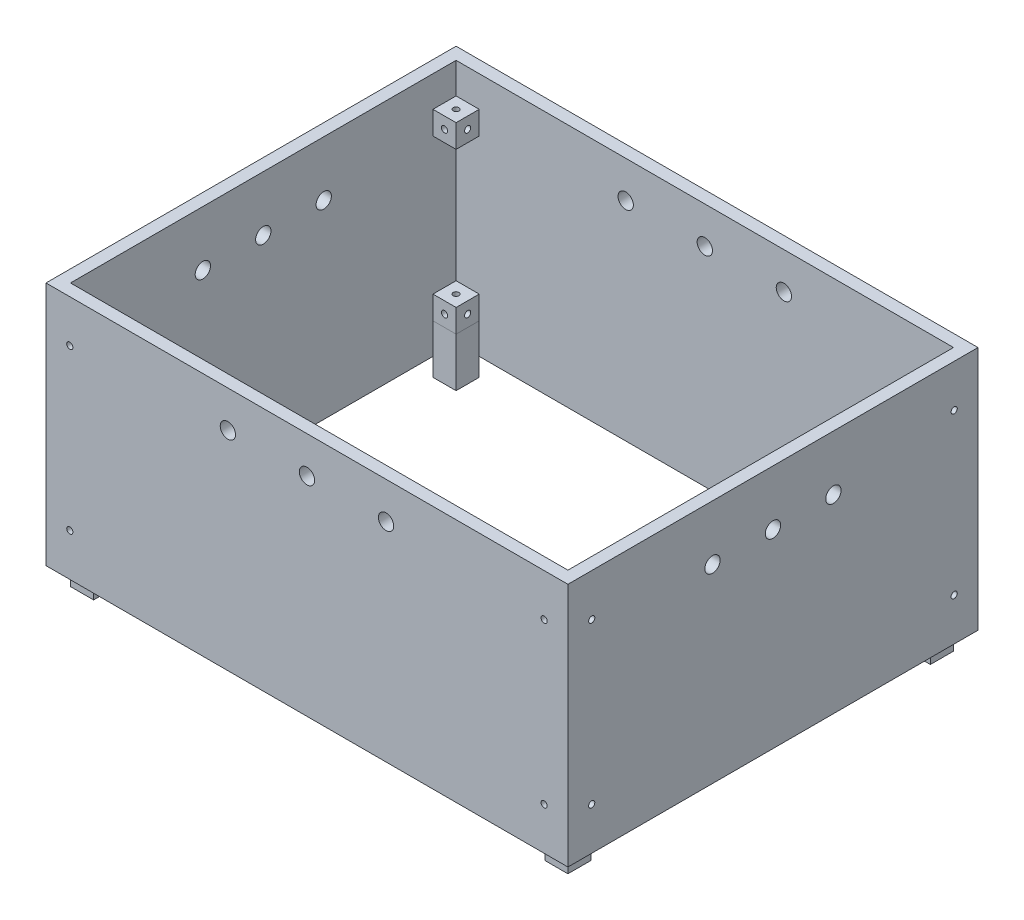
SolidWorks part; units mm, degrees
ref_plane "Front Plane" through (0, 0, 0) normal (0, 0, 1) x (1, 0, 0)
ref_plane "Top Plane" through (0, 0, 0) normal (0, 1, 0) x (1, 0, 0)
ref_plane "Right Plane" through (0, 0, 0) normal (1, 0, 0) x (0, 0, -1)
sketch "Sketch1" plane through (0, 0, 0) normal (0, 1, 0) x (1, 0, 0)
  line L1 (0, 0) -> (270.7, 0)
  line L2 (0, 0) -> (0, 212.7)
  line L3 (0, 212.7) -> (270.7, 212.7)
  line L4 (270.7, 0) -> (270.7, 212.7)
  line L5 (6.35, 6.35) -> (264.35, 6.35)
  line L6 (6.35, 6.35) -> (6.35, 206.35)
  line L7 (6.35, 206.35) -> (264.35, 206.35)
  line L8 (264.35, 6.35) -> (264.35, 206.35)
  dimension "D3" = 6.35
  dimension "D4" = 6.35
  dimension "D5" = 6.35
  dimension "D6" = 6.35
  dimension "D1" = 258
  dimension "D2" = 200
extrude "Walls" add sketch "Sketch1" along normal blind 127
sketch "Sketch2" plane through (0, 0, 0) normal (0, 0, 1) x (1, 0, 0)
  line L0 (0, 127) -> (270.7, 127) construction
  line L1 (135.35, 127) -> (135.35, 107.95) construction
  line L2 (94.33, 127) -> (94.33, 107.95) construction
  line L3 (0, 127) -> (0, 0) construction
  line L4 (176.3667, 127) -> (176.3667, 107.95) construction
  line L5 (270.7, 127) -> (270.7, 0) construction
  circle A0 centre (135.35, 107.95) radius 3.9687
  circle A1 centre (94.33, 107.95) radius 3.9687
  circle A2 centre (176.3667, 107.95) radius 3.9687
  dimension "D2" = 7.9375
  dimension "D4" = 7.9375
  dimension "D7" = 7.9375
  dimension "D1" = 19.05
  dimension "D3" = 94.33
  dimension "D5" = 19.05
  dimension "D6" = 94.3333
  dimension "D8" = 19.05
extrude "RodHolesHeight" cut sketch "Sketch2" against normal through all
sketch "Sketch4" plane through (0, 0, 0) normal (-1, 0, 0) x (0, 0, 1)
  line L0 (-106.35, 127) -> (-106.35, 98.425) construction
  line L1 (-212.7, 127) -> (0, 127) construction
  line L2 (-137.7, 127) -> (-137.7, 98.425) construction
  line L3 (-75, 127) -> (-75, 98.425) construction
  line L4 (-212.7, 127) -> (-212.7, 0) construction
  line L5 (0, 127) -> (0, 0) construction
  circle A0 centre (-106.35, 98.425) radius 3.9687
  circle A1 centre (-137.7, 98.425) radius 3.9687
  circle A2 centre (-75, 98.425) radius 3.9688
  dimension "D2" = 7.9375
  dimension "D5" = 7.9375
  dimension "D6" = 7.9375
  dimension "D1" = 28.575
  dimension "D3" = 75
  dimension "D4" = 75
  dimension "D7" = 28.575
  dimension "D8" = 28.575
extrude "RodHolesWidth" cut sketch "Sketch4" against normal through all contours A1 | A0 | A2
sketch "Sketch3" plane through (0, 0, -6.35) normal (0, 0, -1) x (-1, 0, 0)
  line L14 (-264.35, 111) -> (-252.35, 111)
  line L15 (-264.35, 111) -> (-264.35, 99)
  line L16 (-264.35, 99) -> (-252.35, 99)
  line L17 (-264.35, 0) -> (-6.35, 0)
  line L18 (-6.35, 0) -> (-6.35, 127)
  line L19 (-6.35, 127) -> (-264.35, 127)
  line L20 (-264.35, 127) -> (-264.35, 0)
  line L21 (-264.35, 0) -> (-6.35, 0)
  line L22 (-6.35, 0) -> (-6.35, 127)
  line L23 (-6.35, 127) -> (-264.35, 127)
  line L24 (-264.35, 127) -> (-264.35, 0)
  line L25 (-252.35, 111) -> (-252.35, 99)
  line L26 (-6.35, 111) -> (-18.35, 111)
  line L27 (-6.35, 111) -> (-6.35, 99)
  line L28 (-6.35, 99) -> (-18.35, 99)
  line L29 (-18.35, 111) -> (-18.35, 99)
  line L30 (-264.35, 28) -> (-252.35, 28)
  line L31 (-264.35, 28) -> (-264.35, 16)
  line L32 (-264.35, 16) -> (-252.35, 16)
  line L33 (-252.35, 28) -> (-252.35, 16)
  line L34 (-6.35, 28) -> (-18.35, 28)
  line L35 (-6.35, 28) -> (-6.35, 16)
  line L36 (-6.35, 16) -> (-18.35, 16)
  line L37 (-18.35, 28) -> (-18.35, 16)
  point P20 (-258.35, 16)
  line M35 (-264.35, 127) -> (-264.35, 0)
  dimension "D2" = 12
  dimension "D3" = 16
  dimension "D4" = 16
extrude "ModdingCube" add sketch "Sketch3" along normal blind 12 contours L25 L14 L16 M35 | L33 L30 L24 L32 | L34 L37 L36 L22 | L26 L29 L28 L22 region at (258.35, 105, -6.35) region at (258.35, 22, -6.35) region at (12.35, 105, -6.35) region at (12.35, 22, -6.35)
sketch "Sketch11" plane through (0, 0, -18.35) normal (0, 0, -1) x (-1, 0, 0)
  line L0 (-258.35, 111) -> (-258.35, 105) construction
  line L1 (-264.35, 111) -> (-252.35, 111) construction
  line L2 (-258.35, 105) -> (-252.35, 105) construction
  line L3 (-252.35, 111) -> (-252.35, 99) construction
  line L4 (-12.35, 111) -> (-12.35, 105) construction
  line L5 (-6.35, 111) -> (-18.35, 111) construction
  line L6 (-12.35, 105) -> (-18.35, 105) construction
  line L7 (-18.35, 111) -> (-18.35, 99) construction
  line L8 (-12.35, 28) -> (-12.35, 22) construction
  line L9 (-6.35, 28) -> (-18.35, 28) construction
  line L10 (-12.35, 22) -> (-18.35, 22) construction
  line L11 (-18.35, 28) -> (-18.35, 16) construction
  line L12 (-258.35, 28) -> (-258.35, 22) construction
  line L13 (-264.35, 28) -> (-252.35, 28) construction
  line L14 (-258.35, 22) -> (-252.35, 22) construction
  line L15 (-252.35, 28) -> (-252.35, 16) construction
  line L16 (-252.35, 22) -> (-258.35, 22) construction
  circle A1 centre (-258.35, 105) radius 1.6
  circle A2 centre (-258.35, 22) radius 1.6
  circle A3 centre (-12.35, 105) radius 1.6
  circle A4 centre (-12.35, 22) radius 1.6
  dimension "D1" = 3.2
extrude "Cut-Extrude1" cut sketch "Sketch11" against normal through all both and the other way through all contours A2 | A1 | A3 | A4
sketch "Sketch17" plane through (0, 28, 0) normal (0, 1, 0) x (1, 0, 0)
  line L0 (12.35, 18.35) -> (12.35, 12.35) construction
  line L1 (6.35, 18.35) -> (18.35, 18.35) construction
  line L2 (12.35, 12.35) -> (18.35, 12.35) construction
  line L3 (18.35, 18.35) -> (18.35, 6.35) construction
  line L4 (258.35, 18.35) -> (258.35, 12.35) construction
  line L5 (264.35, 18.35) -> (252.35, 18.35) construction
  line L6 (258.35, 12.35) -> (252.35, 12.35) construction
  line L7 (252.35, 18.35) -> (252.35, 6.35) construction
  circle A0 centre (12.35, 12.35) radius 1.5
  circle A1 centre (258.35, 12.35) radius 1.6
  dimension "D2" = 3.2
  dimension "D1" = 3
extrude "Cut-Extrude4" cut sketch "Sketch17" against normal through all both and the other way through all
sketch "Sketch15" plane through (252.35, 0, 0) normal (-1, 0, 0) x (0, 0, 1)
  line L0 (-12.35, 111) -> (-12.35, 105) construction
  line L1 (-18.35, 111) -> (-6.35, 111) construction
  line L2 (-12.35, 105) -> (-18.35, 105) construction
  line L3 (-18.35, 111) -> (-18.35, 99) construction
  line L5 (-12.35, 28) -> (-12.35, 22) construction
  line L6 (-18.35, 28) -> (-6.35, 28) construction
  line L7 (-12.35, 22) -> (-18.35, 22) construction
  line L8 (-18.35, 28) -> (-18.35, 16) construction
  circle A0 centre (-12.35, 105) radius 1.6
  circle A1 centre (-12.35, 22) radius 1.6
  dimension "D1" = 3.2
  dimension "D2" = 3.2
extrude "Cut-Extrude2" cut sketch "Sketch15" against normal through all both and the other way through all
ref_plane "Plane2" through (0, 0, -106.35) normal (0, 0, -1) x (-1, 0, 0)
mirror "Mirror6" about plane through (0, 0, -106.35) normal (0, 0, -1) of "Cut-Extrude2", "Cut-Extrude4", "Cut-Extrude1", "ModdingCube"
sketch "Sketch18" plane through (0, 16, 0) normal (0, -1, 0) x (1, 0, 0)
  line L1 (6.35, -6.35) -> (18.35, -6.35)
  line L2 (6.35, -6.35) -> (6.35, -18.35)
  line L3 (6.35, -18.35) -> (18.35, -18.35)
  line L4 (18.35, -6.35) -> (18.35, -18.35)
  line L5 (6.35, -206.35) -> (18.35, -206.35)
  line L6 (6.35, -206.35) -> (6.35, -194.35)
  line L7 (6.35, -194.35) -> (18.35, -194.35)
  line L8 (18.35, -206.35) -> (18.35, -194.35)
  line L9 (264.35, -206.35) -> (252.35, -206.35)
  line L10 (264.35, -206.35) -> (264.35, -194.35)
  line L11 (264.35, -194.35) -> (252.35, -194.35)
  line L12 (252.35, -206.35) -> (252.35, -194.35)
  line L13 (264.35, -6.35) -> (252.35, -6.35)
  line L14 (264.35, -6.35) -> (264.35, -18.35)
  line L15 (264.35, -18.35) -> (252.35, -18.35)
  line L16 (252.35, -6.35) -> (252.35, -18.35)
extrude "Pegs" add sketch "Sketch18" along normal blind 25.4 separate body
equation "\"Length\"= 283mm"
equation "\"Width\"= 225mm"
equation "\"WallThickness\"= 12.5mm"
equation "\"UpperWaterJacketThickness\"= 28mm"
equation "\"SpacerHeight\"= 80.2mm"
equation "\"SpacerCornerWidth\"= 10mm"
equation "\"SpacerCornerHeight\"= 60.16mm"
equation "\"SpacerPegDiameter\"= 10mm"
equation "\"SpacerPegHeight\"= 10mm"
equation "\"TubingShort\"= 110mm"
equation "\"TubingLong\"= 175mm"
equation "\"PlateLength\"= 252mm"
equation "\"PlateWidth\"= 190mm"
equation "\"PlateHoleDiameter\"= 5.9mm"
equation "\"PlateHoleBottom\"= 2mm"
equation "\"PlateHoleSide\"= 1.55mm"
equation "\"PlateHoleSpacing\"= 3.1mm"
equation "\"PlateThickness\"= 1.55mm"
equation "\"ReservoirBottom\"= 12.5mm"
equation "\"ReservoirSupportWidth\"= 12mm"
equation "\"ReservoirSupportHeight\"= 15.1mm"
equation "\"ReservoirSupportPlacementHeight\"= 50mm"
equation "\"ReservoirHoleDiameter\"= 12.7mm"
equation "\"ReservoirHoleRight\"= 25mm"
equation "\"ReservoirHoleTop\"= \"ReservoirSupportPlacementHeight\""
equation "\"ReservoirHeight\"= 90mm"
equation "\"ReservoirPortBottom\"= 4mm"
equation "\"ReservoirPortTop\"= 10mm"
equation "\"ReservoirPortWidth\"= 101mm"
equation "\"D3@Sketch1\"=\"CustomSpacerWallThickness\""
equation "\"D4@Sketch1\"=\"CustomSpacerWallThickness\""
equation "\"CustomSpacerWallThickness\"= 0.25in"
equation "\"D5@Sketch1\"=\"CustomSpacerWallThickness\""
equation "\"D6@Sketch1\"=\"CustomSpacerWallThickness\""
equation "\"CustomSpacerHeight\"= 5in"
equation "\"D1@Walls\" = \"CustomSpacerHeight\""
equation "\"CustomSpacerRodHoleHeight\"= .75in"
equation "\"CustomSpacerRodHoleDiameter\"= .3125in"
equation "\"D4@Sketch2\"=\"CustomSpacerRodHoleDiameter\""
equation "\"D5@Sketch2\"=\"CustomSpacerRodHoleHeight\""
equation "\"D2@Sketch2\"=\"CustomSpacerRodHoleDiameter\""
equation "\"D6@Sketch2\"=\"Length\"/3"
equation "\"D7@Sketch2\"=\"CustomSpacerRodHoleDiameter\""
equation "\"D8@Sketch2\"=\"CustomSpacerRodHoleHeight\""
equation "\"ScrewBlockSide\"= 12mm"
equation "\"D2@Sketch3\"=\"ScrewBlockSide\""
equation "\"ScrewBlockUpperHeight\"= 16mm"
equation "\"D3@Sketch3\"=\"ScrewBlockUpperHeight\""
equation "\"ScrewBlockLowerHeight\"= 16mm"
equation "\"D4@Sketch3\"=\"ScrewBlockLowerHeight\""
equation "\"D1@ModdingCube\" = \"ScrewBlockSide\""
equation "\"InternalLength\"= \"Length\" - ( 2 * \"WallThickness\" )"
equation "\"D1@Sketch1\"=\"InternalLength\""
equation "\"InternalWidth\"= \"Width\" - ( 2 * \"WallThickness\" )"
equation "\"D2@Sketch1\"=\"InternalWidth\""
equation "\"D1@Sketch4\"=\"CustomSpacerRodHoleHeight\"+\"CustomSpacerRodHoleDiameter\"+0.0625in"
equation "\"D2@Sketch4\"=\"CustomSpacerRodHoleDiameter\""
equation "\"D3@Sketch4\"=\"Width\"/3"
equation "\"D4@Sketch4\"=\"Width\"/3"
equation "\"D5@Sketch4\"=\"CustomSpacerRodHoleDiameter\""
equation "\"D6@Sketch4\"=\"CustomSpacerRodHoleDiameter\""
equation "\"D7@Sketch4\"=\"CustomSpacerRodHoleHeight\"+\"CustomSpacerRodHoleDiameter\"+0.0625in"
equation "\"D8@Sketch4\"=\"CustomSpacerRodHoleHeight\"+\"CustomSpacerRodHoleDiameter\"+0.0625in"
equation "\"CustomSpacerPegHeight\"= 1in"
equation "\"CustomSpacerScrewBore\"=3.2mm"
equation "\"D1@Sketch11\"=\"CustomSpacerScrewBore\""
equation "\"D1\"= \"ScrewBlockSide\" / 2"
equation "\"D1@Sketch15\"=\"CustomSpacerScrewBore\""
equation "\"D2@Sketch15\"=\"CustomSpacerScrewBore\""
equation "\"D2@Sketch17\"=\"CustomSpacerScrewBore\""
equation "\"D1@Pegs\" = \"CustomSpacerPegHeight\""
equation "\"CustomSpacerScrewDepth\"=10mm"
